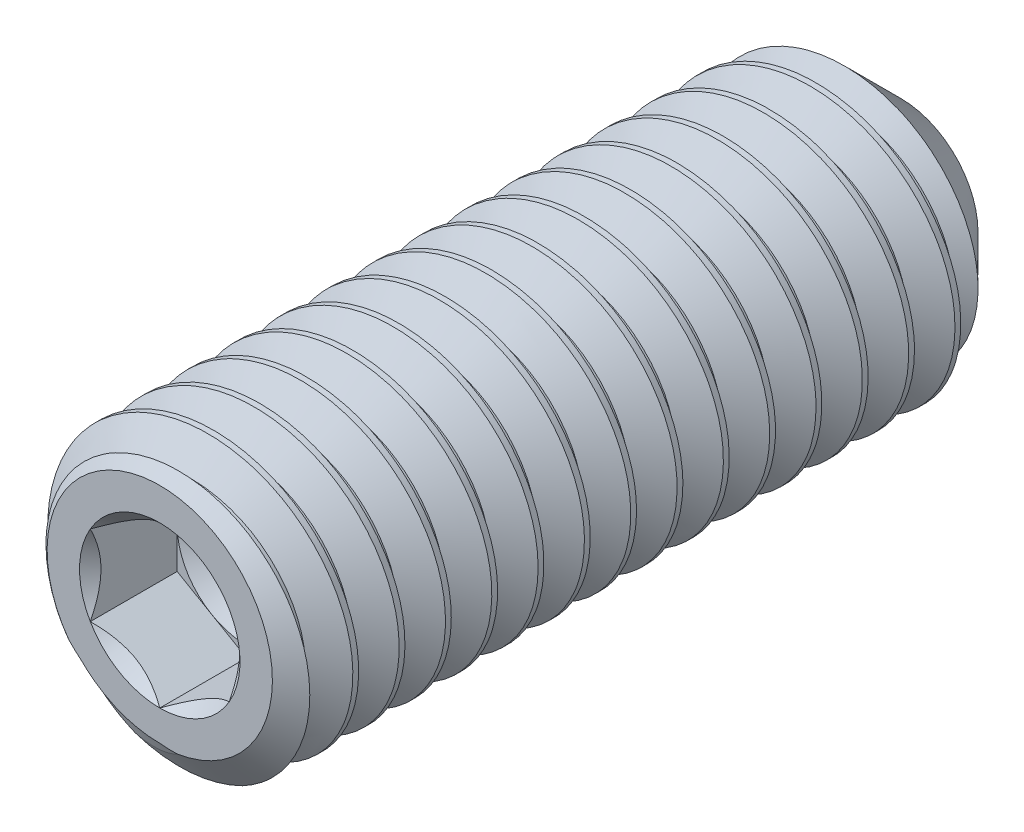
SolidWorks part; units mm, degrees
ref_plane "Front" through (0, 0, 0) normal (0, 0, 1) x (1, 0, 0)
ref_plane "Top" through (0, 0, 0) normal (0, 1, 0) x (1, 0, 0)
ref_plane "Right" through (0, 0, 0) normal (1, 0, 0) x (0, 0, -1)
sketch "Sketch22" plane through (0, 0, 0) normal (1, 0, 0) x (0, 0, -1)
  line L0 (-5.9528, 0) -> (-5.9528, 1.9304)
  line L1 (-5.9528, 1.9304) -> (-5.6148, 2.413)
  line L2 (-5.6148, 2.413) -> (5.6565, 2.413)
  line L3 (5.6565, 2.413) -> (6.7472, 1.3222)
  line L4 (6.7472, 1.3222) -> (5.9528, 0)
  line L5 (5.9528, 0) -> (-5.9528, 0)
  line L6 (5.9528, 0) -> (6.7472, 0) construction
  line L7 (6.7472, 0) -> (6.7472, 1.3222) construction
  line L8 (6.7472, -1.3222) -> (5.9528, 0) construction
  line L9 (-5.6148, -2.413) -> (5.6565, -2.413) construction
  dimension "Dia" = 4.826
  dimension "Length" = 12.7
  dimension "D3" = 35
  dimension "D5" = 118
  dimension "D6" = 45
  dimension "D7" = 3.8608
revolve "Revolve1" add sketch "Sketch22" angle 360 about L6
ref_plane "Plane1" through (0, 0, -6.7472) normal (0, 0, 1) x (1, 0, 0)
sketch "Sketch27" plane through (0, 0, -6.7472) normal (0, 0, 1) x (1, 0, 0)
  circle A0 centre (0, 0) radius 2.413 construction
  circle A1 centre (0, 0) radius 2.413
curve "Helix/Spiral1" pitch 0.7937 height 13.4937 radius 2.413 centre (0, 0, -6.7472) axis (0, 0, 1) start towards (0, 1, 0)
sketch "Sketch28" plane through (0, 0, 0) normal (1, 0, 0) x (0, 0, -1)
  line L0 (6.7472, 2.413) -> (7.4418, 2.413)
  line L1 (7.4418, 2.413) -> (7.1441, 1.8974)
  line L2 (7.1441, 1.8974) -> (7.0449, 1.8974)
  line L3 (7.0449, 1.8974) -> (6.7472, 2.413)
  line L4 (6.8961, 2.1552) -> (7.2929, 2.1552) construction
  line L6 (-5.6148, 2.413) -> (5.6565, 2.413) construction
  line L7 (6.7472, 2.6543) -> (6.7472, -2.6543) construction
  dimension "D1" = 0.0992
  dimension "D3" = 60
  dimension "D2" = 0.3969
sweep "Cut-Sweep2" cut profiles "Sketch28" path "Helix/Spiral1" align with end faces yes
sketch "Sketch23" plane through (0, 0, 5.9528) normal (0, 0, 1) x (1, 0, 0)
  line L1 (0, 1.3748) -> (-1.1906, 0.6874)
  line L2 (-1.1906, 0.6874) -> (-1.1906, -0.6874)
  line L3 (-1.1906, -0.6874) -> (0, -1.3748)
  line L4 (0, -1.3748) -> (1.1906, -0.6874)
  line L5 (1.1906, -0.6874) -> (1.1906, 0.6874)
  line L6 (1.1906, 0.6874) -> (0, 1.3748)
  circle A0 centre (0, 0) radius 1.1906 construction
  dimension "Hex" = 2.3813
extrude "Cut-Extrude10" cut sketch "Sketch23" against normal blind 1.4883
sketch "Sketch24" plane through (0, 0, 5.9528) normal (0, 0, 1) x (1, 0, 0)
  circle A0 centre (0, 0) radius 1.3748
extrude "Cut-Extrude11" cut sketch "Sketch24" against normal through all draft 45
sketch "Sketch26" plane through (0, 0, 4.4645) normal (0, 0, 1) x (1, 0, 0)
  circle A0 centre (0, 0) radius 1.1906 construction
  circle A1 centre (0, 0) radius 1.1906
extrude "Cut-Extrude12" cut sketch "Sketch26" against normal through all draft 60
sketch "Sketch30" plane through (0, 0, 0) normal (1, 0, 0) x (0, 0, -1)
  line L0 (-5.6148, 2.413) -> (5.6565, 2.413) construction
  line L1 (-5.9528, 0) -> (-5.9528, 1.9304) construction
  line L2 (6.7472, 0) -> (6.7472, 1.3222) construction
  line L3 (-5.6148, -2.413) -> (5.6565, -2.413) construction
  point P0 (-5.9528, 2.413)
  point P1 (6.7472, 2.413)
  point P2 (6.7472, -2.413)
  point P11 (3.9691, -2.413)
  dimension "D1" = 2.7781
sketch "Sketch31" plane through (0, 0, 0) normal (1, 0, 0) x (0, 0, -1)
  line L2 (5.9528, 0) -> (6.7472, -1.3222)
  line L3 (6.7472, 1.3222) -> (5.9528, 0)
ref_plane "Plane2" through (-1.5588, -1.1386, 5.9528) normal (0.5898, -0.8075, 0) x (-0.8075, -0.5898, 0)
equation "\"D7@Sketch22\"=\"Dia@Sketch22\"*.8"
equation "\"D1@Sketch28\" = \"D4@Helix/Spiral1\" * .125"
equation "\"D3@Helix/Spiral1\" = \"Length@Sketch22\" + \"D4@Helix/Spiral1\""
equation "\"D1@Sketch30\" = \"D4@Helix/Spiral1\" * 3.5"
equation "\"hex Depth@Cut-Extrude10\" = \"Hex@Sketch23\" * .625"
equation "\"D2@Sketch28\" = \"D4@Helix/Spiral1\" * .5"
